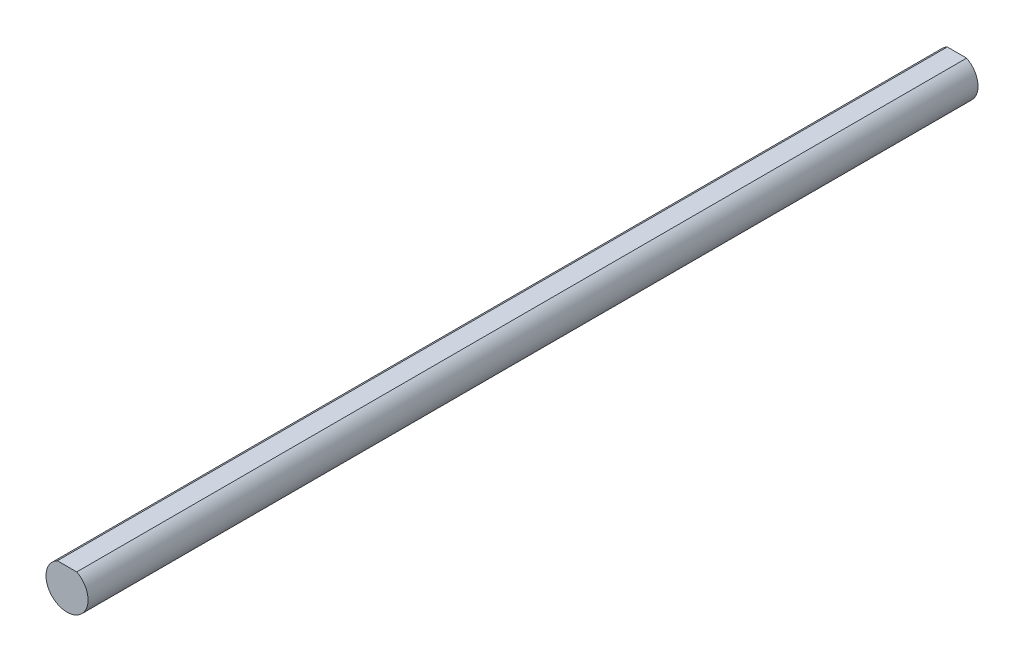
SolidWorks part; units mm, degrees
material "AISI 1020"
ref_plane "Front" through (0, 0, 0) normal (0, 0, 1) x (1, 0, 0)
ref_plane "Top" through (0, 0, 0) normal (0, 1, 0) x (1, 0, 0)
ref_plane "Right" through (0, 0, 0) normal (1, 0, 0) x (0, 0, -1)
ref_axis "side-side" through (80.9, 0, 0) along (-1, 0, 0)
ref_axis "up-down" through (0, 50, 0) along (0, -1, 0)
ref_axis "front-back" through (0, 0, -80.9) along (0, 0, 1)
sketch3d "3DSketch1"
  line L2 (1.0878, 2.1, 50) -> (-1.0878, 2.1, 50)
  line L3 (1.0878, 2.1, -50) -> (1.0878, 2.1, 50)
  arc A2 (-1.0878, 2.1, 50) -> (1.0878, 2.1, 50) centre (0, 0, 50) ccw
  point P6 (0, 0, 52.365)
sketch "Sketch1" plane through (0, 0, 0) normal (0, 0, 1) x (1, 0, 0)
  line L0 (1.0878, 2.1) -> (-1.0878, 2.1) construction
  line L1 (1.0878, 2.1) -> (-1.0878, 2.1)
  arc A0 (-1.0878, 2.1) -> (1.0878, 2.1) centre (0, 0) ccw construction
  arc A1 (-1.0878, 2.1) -> (1.0878, 2.1) centre (0, 0) ccw
  dimension "D1" = 4.73
extrude "Boss-Extrude1" add sketch "Sketch1" along normal up to vertex (50 mm away) and the other way up to vertex (50 mm away) up to point (1.0878, 2.1, 50) other way up to point (1.0878, 2.1, -50)
